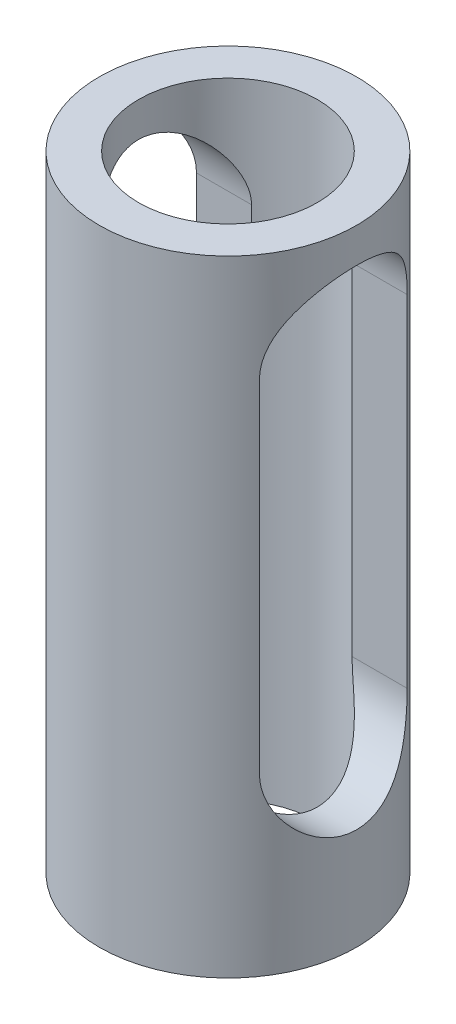
SolidWorks part; units mm, degrees
ref_plane "Front Plane" through (0, 0, 0) normal (0, 0, 1) x (1, 0, 0)
ref_plane "Top Plane" through (0, 0, 0) normal (0, 1, 0) x (1, 0, 0)
ref_plane "Right Plane" through (0, 0, 0) normal (1, 0, 0) x (0, 0, -1)
sketch "Sketch1" plane through (0, 0, 0) normal (0, 1, 0) x (1, 0, 0)
  circle A0 centre (0, 0) radius 7.9883
  circle A1 centre (0, 0) radius 11.5
  dimension "D1" = 15.9766
  dimension "D2" = 23
extrude "Boss-Extrude1" add sketch "Sketch1" along normal blind 55.88
ref_plane "Plane1" through (-11.5, 0, 0) normal (-1, 0, 0) x (0, 0, 1)
sketch "Sketch2" plane through (-11.5, 0, 0) normal (-1, 0, 0) x (0, 0, 1)
  line L0 (0, 46.1758) -> (0, 15.6995) construction
  line L1 (6.604, 46.1758) -> (6.604, 15.6995)
  line L2 (-6.604, 46.1758) -> (-6.604, 15.6995)
  arc A0 (6.604, 46.1758) -> (-6.604, 46.1758) centre (0, 46.1758) ccw
  arc A1 (-6.604, 15.6995) -> (6.604, 15.6995) centre (0, 15.6995) ccw
  point P3 (0, 30.9377)
  dimension "D1" = 6.604
extrude "Cut-Extrude1" cut sketch "Sketch2" against normal blind 55.88
